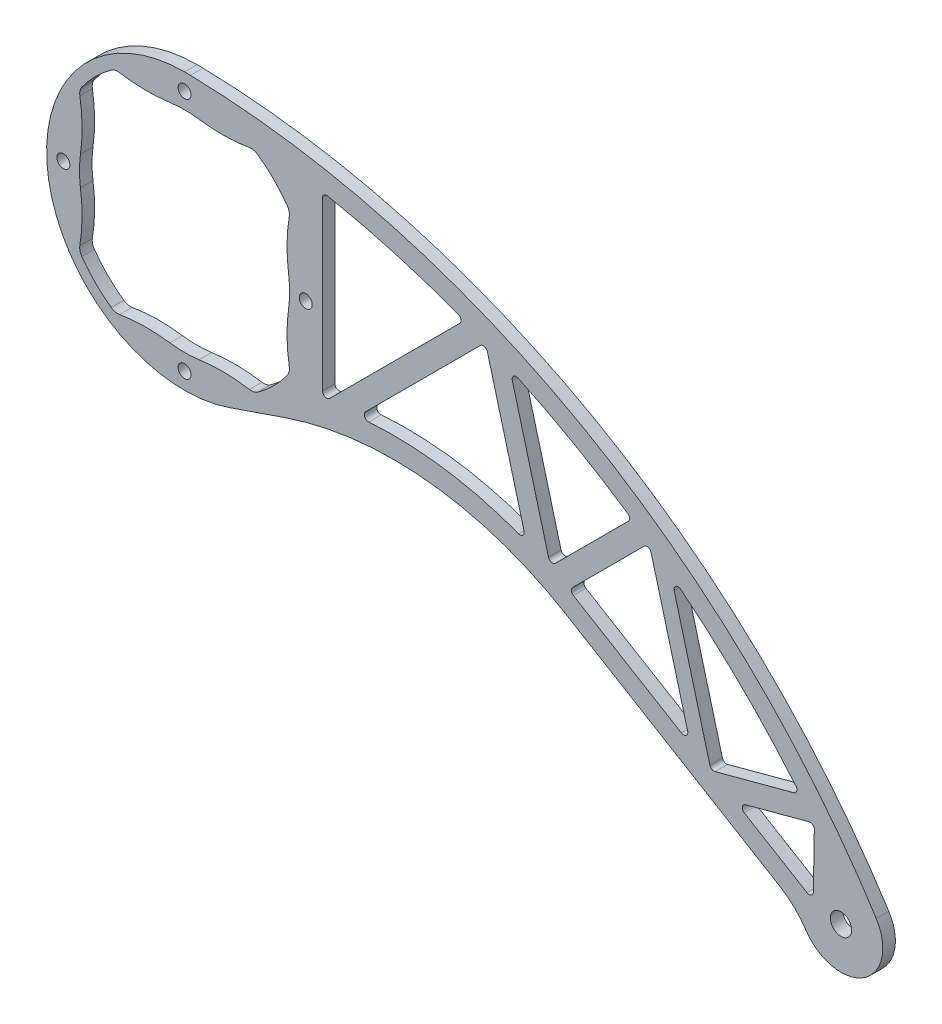
SolidWorks part; units mm, degrees
material "6061 合金"
ref_plane "前视基准面" through (0, 0, 0) normal (0, 0, 1) x (1, 0, 0)
ref_plane "上视基准面" through (0, 0, 0) normal (0, 1, 0) x (1, 0, 0)
ref_plane "右视基准面" through (0, 0, 0) normal (1, 0, 0) x (0, 0, -1)
other "Configuration Table"
sketch "草图2" plane through (0, 0, 0) normal (0, 0, 1) x (1, 0, 0)
  line L1 (10.7304, -31.2067) -> (23.987, -26.6485)
  line L2 (91.2325, -33.7454) -> (142.3676, -64.5004)
  line L3 (0, 0) -> (154.4016, 0) construction
  line L4 (0, 0) -> (157.0595, -65.0562) construction
  line L5 (0, 0) -> (0, -130.9869) construction
  arc A24 (0, 33) -> (10.7304, -31.2067) centre (0, 0) ccw
  arc A25 (148.7262, -70.5839) -> (165.4995, -59.6928) centre (157.0595, -65.0562) ccw
  arc A26 (1.4146, 32.9833) -> (165.4995, -59.6928) centre (-3.3007, -166.9611) cw
  circle A27 centre (-29, 0) radius 1.55
  arc A28 (23.987, -26.6485) -> (91.2325, -33.7454) centre (50, -102.3011) cw
  arc A29 (142.3676, -64.5004) -> (148.7262, -70.5839) centre (132.0595, -81.6393) cw
  arc A30 (1.4146, 32.9833) -> (0, 33) centre (0, -27) ccw
  arc A32 (-24.8547, -15.5614) -> (-24.7074, -3.4705) centre (-64.3186, -9.0345) ccw construction
  arc A33 (-24.8547, -15.5614) -> (-24.4235, -17.4211) centre (-22.3882, -15.9693) ccw construction
  arc A34 (-24.4235, -17.4211) -> (-17.4211, -24.4235) centre (0, 0) ccw construction
  arc A35 (-17.4211, -24.4235) -> (-15.5614, -24.8547) centre (-15.9693, -22.3882) ccw construction
  arc A36 (-3.4705, -24.7074) -> (-15.5614, -24.8547) centre (-9.0345, -64.3186) ccw construction
  arc A37 (-3.4705, -24.7074) -> (3.4705, -24.7074) centre (0, 0) ccw construction
  arc A38 (15.5614, -24.8547) -> (3.4705, -24.7074) centre (9.0345, -64.3186) ccw construction
  arc A39 (15.5614, -24.8547) -> (17.4211, -24.4235) centre (15.9693, -22.3882) ccw construction
  arc A40 (17.4211, -24.4235) -> (24.4235, -17.4211) centre (0, 0) ccw construction
  arc A41 (24.4235, -17.4211) -> (24.8547, -15.5614) centre (22.3882, -15.9693) ccw construction
  arc A42 (24.7074, -3.4705) -> (24.8547, -15.5614) centre (64.3186, -9.0345) ccw construction
  arc A43 (24.7074, -3.4705) -> (24.7074, 3.4705) centre (0, 0) ccw construction
  arc A44 (24.8547, 15.5614) -> (24.7074, 3.4705) centre (64.3186, 9.0345) ccw construction
  arc A45 (24.8547, 15.5614) -> (24.4235, 17.4211) centre (22.3882, 15.9693) ccw construction
  arc A46 (24.4235, 17.4211) -> (17.4211, 24.4235) centre (0, 0) ccw construction
  arc A47 (17.4211, 24.4235) -> (15.5614, 24.8547) centre (15.9693, 22.3882) ccw construction
  arc A48 (3.4705, 24.7074) -> (15.5614, 24.8547) centre (9.0345, 64.3186) ccw construction
  arc A49 (3.4705, 24.7074) -> (-3.4705, 24.7074) centre (0, 0) ccw construction
  arc A50 (-15.5614, 24.8547) -> (-3.4705, 24.7074) centre (-9.0345, 64.3186) ccw construction
  arc A51 (-15.5614, 24.8547) -> (-17.4211, 24.4235) centre (-15.9693, 22.3882) ccw construction
  arc A52 (-17.4211, 24.4235) -> (-24.4235, 17.4211) centre (0, 0) ccw construction
  arc A53 (-24.4235, 17.4211) -> (-24.8547, 15.5614) centre (-22.3882, 15.9693) ccw construction
  arc A54 (-24.7074, 3.4705) -> (-24.8547, 15.5614) centre (-64.3186, 9.0345) ccw construction
  arc A55 (-24.7074, 3.4705) -> (-24.7074, -3.4705) centre (0, 0) ccw construction
  arc A56 (-17.4792, 24.5049) -> (-24.5049, 17.4792) centre (0, 0) ccw
  arc A57 (-24.5049, 17.4792) -> (-24.9533, 15.5451) centre (-22.3882, 15.9693) ccw
  arc A58 (-24.8065, 3.4845) -> (-24.9533, 15.5451) centre (-64.3186, 9.0345) ccw
  arc A59 (-24.8065, 3.4845) -> (-24.8065, -3.4845) centre (0, 0) ccw
  arc A60 (-24.9533, -15.5451) -> (-24.8065, -3.4845) centre (-64.3186, -9.0345) ccw
  arc A61 (-24.9533, -15.5451) -> (-24.5049, -17.4792) centre (-22.3882, -15.9693) ccw
  arc A62 (-24.5049, -17.4792) -> (-17.4792, -24.5049) centre (0, 0) ccw
  arc A63 (-17.4792, -24.5049) -> (-15.5451, -24.9533) centre (-15.9693, -22.3882) ccw
  arc A64 (-3.4845, -24.8065) -> (-15.5451, -24.9533) centre (-9.0345, -64.3186) ccw
  arc A65 (-3.4845, -24.8065) -> (3.4845, -24.8065) centre (0, 0) ccw
  arc A66 (15.5451, -24.9533) -> (3.4845, -24.8065) centre (9.0345, -64.3186) ccw
  arc A67 (15.5451, -24.9533) -> (17.4792, -24.5049) centre (15.9693, -22.3882) ccw
  arc A68 (17.4792, -24.5049) -> (24.5049, -17.4792) centre (0, 0) ccw
  arc A69 (24.5049, -17.4792) -> (24.9533, -15.5451) centre (22.3882, -15.9693) ccw
  arc A70 (24.8065, -3.4845) -> (24.9533, -15.5451) centre (64.3186, -9.0345) ccw
  arc A71 (24.8065, -3.4845) -> (24.8065, 3.4845) centre (0, 0) ccw
  arc A72 (24.9533, 15.5451) -> (24.8065, 3.4845) centre (64.3186, 9.0345) ccw
  arc A73 (24.9533, 15.5451) -> (24.5049, 17.4792) centre (22.3882, 15.9693) ccw
  arc A74 (24.5049, 17.4792) -> (17.4792, 24.5049) centre (0, 0) ccw
  arc A75 (17.4792, 24.5049) -> (15.5451, 24.9533) centre (15.9693, 22.3882) ccw
  arc A76 (3.4845, 24.8065) -> (15.5451, 24.9533) centre (9.0345, 64.3186) ccw
  arc A77 (3.4845, 24.8065) -> (-3.4845, 24.8065) centre (0, 0) ccw
  arc A78 (-15.5451, 24.9533) -> (-3.4845, 24.8065) centre (-9.0345, 64.3186) ccw
  arc A79 (-15.5451, 24.9533) -> (-17.4792, 24.5049) centre (-15.9693, 22.3882) ccw
  circle A80 centre (0, 0) radius 29 construction
  circle A81 centre (0, 29) radius 1.55
  circle A82 centre (0, -29) radius 1.55
  arc A83 (15.5614, -24.8547) -> (3.4705, -24.7074) centre (9.0345, -64.3186) ccw construction
  circle A84 centre (29, 0) radius 1.55
  point P51 (147.0595, -65.0562)
  dimension "D3" = 3.1
  dimension "D5" = 66
  dimension "D6" = 20
  dimension "D7" = 80
  dimension "D9" = 20
  dimension "D10" = 200
  dimension "D11" = 60
  dimension "D13" = 50
  dimension "D1" = 170
  dimension "D2" = 130
  dimension "D4" = 29
  dimension "D8" = 22.5
  dimension "D12" = 0.1
  dimension "D14" = 25
extrude "凸台-拉伸1" add sketch "草图2" along normal blind 3
sketch "草图7" plane through (0, 0, 3) normal (0, 0, 1) x (1, 0, 0)
  circle A0 centre (157.0595, -65.0562) radius 2.55
  arc A1 (148.7262, -70.5839) -> (165.4995, -59.6928) centre (157.0595, -65.0562) ccw construction
  dimension "D1" = 5.1
extrude "切除-拉伸2" cut sketch "草图7" against normal blind 5
sketch "草图9" plane through (0, 0, 3) normal (0, 0, 1) x (1, 0, 0)
  line L0 (93.8095, -29.4607) -> (77.7146, -19.7805) construction
  line L2 (10.7304, -31.2067) -> (23.987, -26.6485)
  line L3 (91.2325, -33.7454) -> (142.3676, -64.5004)
  line L6 (33, 23.4192) -> (33, -16.6042)
  line L7 (34.7071, -17.3113) -> (65.8687, 13.8502)
  line L8 (70.7773, 11.6878) -> (43.2854, -15.8041)
  line L9 (72.4503, 11.2395) -> (81.2349, -21.5452)
  line L10 (78.4208, 8.276) -> (87.0701, -24.0039)
  line L11 (88.7431, -24.4522) -> (106.1707, -7.0247)
  line L12 (14.8183, -31.2257) -> (-22.149, -67.7394) construction
  line L13 (-23.9266, -76.5229) -> (-33.3984, -85.8785) construction
  line L14 (109.9456, -10.3208) -> (92.8385, -27.4279)
  line L15 (93.0302, -28.992) -> (118.8884, -44.5443)
  line L16 (93.8095, -29.4607) -> (144.9447, -60.2157) construction
  line L17 (91.2325, -33.7454) -> (142.3676, -64.5004) construction
  line L18 (111.6187, -10.7691) -> (120.3697, -43.4285)
  line L29 (117.1346, -15.8999) -> (125.6886, -47.8239)
  line L30 (93.8095, -29.4607) -> (144.9447, -60.2157)
  line L31 (93.8095, -29.4607) -> (144.9447, -60.2157) construction
  line L32 (126.9133, -48.531) -> (145.7798, -43.4758)
  line L33 (149.4125, -47.6788) -> (134.1757, -51.7615)
  line L34 (150.6712, -48.6626) -> (150.4368, -61.7685)
  line L35 (133.9191, -53.5844) -> (148.9215, -62.6075)
  arc A1 (79.917, -22.74) -> (44.0624, -17.5087) centre (50, -102.3011) ccw
  arc A7 (148.7262, -70.5839) -> (142.3676, -64.5004) centre (132.0595, -81.6393) ccw
  arc A8 (148.7262, -70.5839) -> (165.4995, -59.6928) centre (157.0595, -65.0562) ccw
  arc A9 (165.4995, -59.6928) -> (1.4146, 32.9833) centre (-3.3007, -166.9611) ccw
  arc A10 (1.4146, 32.9833) -> (0, 33) centre (0, -27) ccw
  arc A11 (117.1346, -15.8999) -> (118.7263, -14.861) centre (118.1005, -15.641) cw
  arc A12 (0, 33) -> (10.7304, -31.2067) centre (0, 0) ccw
  arc A13 (91.2325, -33.7454) -> (23.987, -26.6485) centre (50, -102.3011) ccw
  arc A15 (148.7262, -70.5839) -> (156.4086, -55.0774) centre (157.0595, -65.0562) ccw construction
  arc A21 (161.2795, -62.3745) -> (1.2967, 27.9847) centre (-3.3007, -166.9611) ccw construction
  arc A22 (93.8095, -29.4607) -> (-33.3984, -85.8785) centre (50, -102.3011) ccw construction
  arc A23 (65.5144, 15.493) -> (34.1923, 24.4006) centre (-3.3007, -166.9611) ccw
  arc A24 (106.0242, -5.4895) -> (79.8129, 9.4394) centre (-3.3007, -166.9611) ccw
  arc A27 (152.8929, -67.82) -> (144.9447, -60.2157) centre (132.0595, -81.6393) ccw construction
  arc A28 (165.4995, -59.6928) -> (1.4146, 32.9833) centre (-3.3007, -166.9611) ccw construction
  arc A29 (1.2967, 27.9847) -> (-23.9266, -76.5229) centre (0, -27) ccw construction
  arc A30 (1.4146, 32.9833) -> (15.1955, 31.0439) centre (0, -27) ccw construction
  circle A31 centre (3.5031, 49.1035) radius 21.5142 construction
  arc A32 (-23.9266, -76.5229) -> (-23.9266, -76.5229) centre (-23.9266, -76.5229) ccw construction
  arc A33 (-23.9266, -76.5229) -> (-23.9266, -76.5229) centre (-23.9266, -76.5229) cw construction
  arc A34 (15.1955, 31.0439) -> (14.8183, -31.2257) centre (0, 0) ccw construction
  arc A35 (91.2325, -33.7454) -> (-22.149, -67.7394) centre (50, -102.3011) ccw construction
  arc A36 (148.7262, -70.5839) -> (142.3676, -64.5004) centre (132.0595, -81.6393) ccw construction
  arc A37 (148.7262, -70.5839) -> (165.4995, -59.6928) centre (157.0595, -65.0562) ccw construction
  arc A38 (152.8929, -67.82) -> (161.2795, -62.3745) centre (157.0595, -65.0562) ccw construction
  arc A42 (92.8385, -27.4279) -> (93.0302, -28.992) centre (93.5456, -28.135) ccw
  arc A43 (109.9456, -10.3208) -> (111.6187, -10.7691) centre (110.6527, -11.0279) cw
  arc A44 (106.1707, -7.0247) -> (106.0242, -5.4895) centre (105.4636, -6.3176) ccw
  arc A45 (78.4208, 8.276) -> (79.8129, 9.4394) centre (79.3867, 8.5348) cw
  arc A46 (87.0701, -24.0039) -> (88.7431, -24.4522) centre (88.036, -23.7451) ccw
  arc A47 (43.2854, -15.8041) -> (44.0624, -17.5087) centre (43.9926, -16.5112) ccw
  arc A48 (70.7773, 11.6878) -> (72.4503, 11.2395) centre (71.4844, 10.9806) cw
  arc A49 (65.8687, 13.8502) -> (65.5144, 15.493) centre (65.1615, 14.5573) ccw
  arc A50 (33, -16.6042) -> (34.7071, -17.3113) centre (34, -16.6042) ccw
  arc A51 (33, 23.4192) -> (34.1923, 24.4006) centre (34, 23.4192) cw
  arc A52 (81.2349, -21.5452) -> (79.917, -22.74) centre (80.269, -21.804) cw
  arc A53 (120.3697, -43.4285) -> (118.8884, -44.5443) centre (119.4038, -43.6873) cw
  arc A58 (145.7798, -43.4758) -> (146.2881, -41.8684) centre (145.521, -42.5099) ccw
  arc A60 (125.6886, -47.8239) -> (126.9133, -48.531) centre (126.6545, -47.5651) ccw
  arc A61 (134.1757, -51.7615) -> (133.9191, -53.5844) centre (134.4345, -52.7274) ccw
  arc A62 (149.4125, -47.6788) -> (150.6712, -48.6626) centre (149.6713, -48.6447) cw
  arc A63 (161.2795, -62.3745) -> (1.2967, 27.9847) centre (-3.3007, -166.9611) ccw
  arc A64 (161.2795, -62.3745) -> (156.4086, -55.0774) centre (-3.3007, -166.9611) ccw construction
  arc A65 (146.2881, -41.8684) -> (118.7263, -14.861) centre (-3.3007, -166.9611) ccw
  arc A66 (152.8929, -67.82) -> (144.9447, -60.2157) centre (132.0595, -81.6393) ccw
  arc A67 (152.8929, -67.82) -> (144.9447, -60.2157) centre (132.0595, -81.6393) ccw construction
  arc A68 (150.4368, -61.7685) -> (148.9215, -62.6075) centre (149.4369, -61.7506) cw
  circle A69 centre (29, 0) radius 1.55 construction
  point P54 (119.853, -45.1244)
  point P60 (91.9338, -28.3326)
  point P63 (111.1704, -9.096)
  point P66 (107.0242, -6.1711)
  point P71 (87.5184, -25.6769)
  point P76 (72.002, 12.9125)
  point P79 (66.9597, 14.9413)
  point P82 (33, -19.0185)
  point P88 (147.2865, -43.0721)
  point P96 (125.9474, -48.7899)
  point P99 (131.9014, -52.3709)
  point P103 (150.6949, -47.3352)
  point P106 (150.4058, -63.5002)
  dimension "D12" = 5
  dimension "D14" = 90
  dimension "D15" = 1
  dimension "D16" = 1
  dimension "D17" = 5
  dimension "D18" = 5
  dimension "D13" = 4
  dimension "D19" = 1
  dimension "D3" = 4
  dimension "D4" = 45
  dimension "D5" = 5
  dimension "D6" = 60
  dimension "D7" = 5
  dimension "D8" = 60
  dimension "D9" = 5
  dimension "D10" = 60
  dimension "D11" = 5
  dimension "D20" = 60
  dimension "D1" = 0
  dimension "D2" = 5
extrude "切除-拉伸4" cut sketch "草图9" against normal through all
sketch "草图10" plane through (0, 0, 3) normal (0, 0, 1) x (1, 0, 0)
  arc A48 (-3.4984, -24.9055) -> (-15.5288, -25.052) centre (-9.0345, -64.3186) ccw
  arc A49 (-17.5372, -24.5863) -> (-15.5288, -25.052) centre (-15.9693, -22.3882) ccw
  arc A50 (-24.5863, -17.5372) -> (-17.5372, -24.5863) centre (0, 0) ccw
  arc A51 (-25.052, -15.5288) -> (-24.5863, -17.5372) centre (-22.3882, -15.9693) ccw
  arc A52 (-25.052, -15.5288) -> (-24.9055, -3.4984) centre (-64.3186, -9.0345) ccw
  arc A53 (-24.9055, 3.4984) -> (-24.9055, -3.4984) centre (0, 0) ccw
  arc A54 (-24.9055, 3.4984) -> (-25.052, 15.5288) centre (-64.3186, 9.0345) ccw
  arc A55 (-24.5863, 17.5372) -> (-25.052, 15.5288) centre (-22.3882, 15.9693) ccw
  arc A56 (-17.5372, 24.5863) -> (-24.5863, 17.5372) centre (0, 0) ccw
  arc A57 (-15.5288, 25.052) -> (-17.5372, 24.5863) centre (-15.9693, 22.3882) ccw
  arc A58 (-15.5288, 25.052) -> (-3.4984, 24.9055) centre (-9.0345, 64.3186) ccw
  arc A59 (3.4984, 24.9055) -> (-3.4984, 24.9055) centre (0, 0) ccw
  arc A60 (3.4984, 24.9055) -> (15.5288, 25.052) centre (9.0345, 64.3186) ccw
  arc A61 (17.5372, 24.5863) -> (15.5288, 25.052) centre (15.9693, 22.3882) ccw
  arc A62 (24.5863, 17.5372) -> (17.5372, 24.5863) centre (0, 0) ccw
  arc A63 (25.052, 15.5288) -> (24.5863, 17.5372) centre (22.3882, 15.9693) ccw
  arc A64 (25.052, 15.5288) -> (24.9055, 3.4984) centre (64.3186, 9.0345) ccw
  arc A65 (24.9055, -3.4984) -> (24.9055, 3.4984) centre (0, 0) ccw
  arc A66 (24.9055, -3.4984) -> (25.052, -15.5288) centre (64.3186, -9.0345) ccw
  arc A67 (24.5863, -17.5372) -> (25.052, -15.5288) centre (22.3882, -15.9693) ccw
  arc A68 (17.5372, -24.5863) -> (24.5863, -17.5372) centre (0, 0) ccw
  arc A69 (15.5288, -25.052) -> (17.5372, -24.5863) centre (15.9693, -22.3882) ccw
  arc A70 (15.5288, -25.052) -> (3.4984, -24.9055) centre (9.0345, -64.3186) ccw
  arc A71 (-3.4984, -24.9055) -> (3.4984, -24.9055) centre (0, 0) ccw
  arc A72 (-3.4984, -24.9055) -> (-15.5288, -25.052) centre (-9.0345, -64.3186) ccw
  arc A73 (-17.5372, -24.5863) -> (-15.5288, -25.052) centre (-15.9693, -22.3882) ccw
  arc A74 (-24.5863, -17.5372) -> (-17.5372, -24.5863) centre (0, 0) ccw
  arc A75 (-25.052, -15.5288) -> (-24.5863, -17.5372) centre (-22.3882, -15.9693) ccw
  arc A76 (-25.052, -15.5288) -> (-24.9055, -3.4984) centre (-64.3186, -9.0345) ccw
  arc A77 (-24.9055, 3.4984) -> (-24.9055, -3.4984) centre (0, 0) ccw
  arc A78 (-24.9055, 3.4984) -> (-25.052, 15.5288) centre (-64.3186, 9.0345) ccw
  arc A79 (-24.5863, 17.5372) -> (-25.052, 15.5288) centre (-22.3882, 15.9693) ccw
  arc A80 (-17.5372, 24.5863) -> (-24.5863, 17.5372) centre (0, 0) ccw
  arc A81 (-15.5288, 25.052) -> (-17.5372, 24.5863) centre (-15.9693, 22.3882) ccw
  arc A82 (-15.5288, 25.052) -> (-3.4984, 24.9055) centre (-9.0345, 64.3186) ccw
  arc A83 (3.4984, 24.9055) -> (-3.4984, 24.9055) centre (0, 0) ccw
  arc A84 (3.4984, 24.9055) -> (15.5288, 25.052) centre (9.0345, 64.3186) ccw
  arc A85 (17.5372, 24.5863) -> (15.5288, 25.052) centre (15.9693, 22.3882) ccw
  arc A86 (24.5863, 17.5372) -> (17.5372, 24.5863) centre (0, 0) ccw
  arc A87 (25.052, 15.5288) -> (24.5863, 17.5372) centre (22.3882, 15.9693) ccw
  arc A88 (25.052, 15.5288) -> (24.9055, 3.4984) centre (64.3186, 9.0345) ccw
  arc A89 (24.9055, -3.4984) -> (24.9055, 3.4984) centre (0, 0) ccw
  arc A90 (24.9055, -3.4984) -> (25.052, -15.5288) centre (64.3186, -9.0345) ccw
  arc A91 (24.5863, -17.5372) -> (25.052, -15.5288) centre (22.3882, -15.9693) ccw
  arc A92 (17.5372, -24.5863) -> (24.5863, -17.5372) centre (0, 0) ccw
  arc A93 (15.5288, -25.052) -> (17.5372, -24.5863) centre (15.9693, -22.3882) ccw
  arc A94 (15.5288, -25.052) -> (3.4984, -24.9055) centre (9.0345, -64.3186) ccw
  arc A95 (-3.4984, -24.9055) -> (3.4984, -24.9055) centre (0, 0) ccw
  dimension "D1" = 0.1
extrude "切除-拉伸5" cut sketch "草图10" against normal through all
mirror "镜向1" about plane through (132.0595, -81.6393, 3) normal (0, 0, -1) of bodies 132
delete or keep bodies "实体-删除/保留 1" type delete bodies bodies 132
